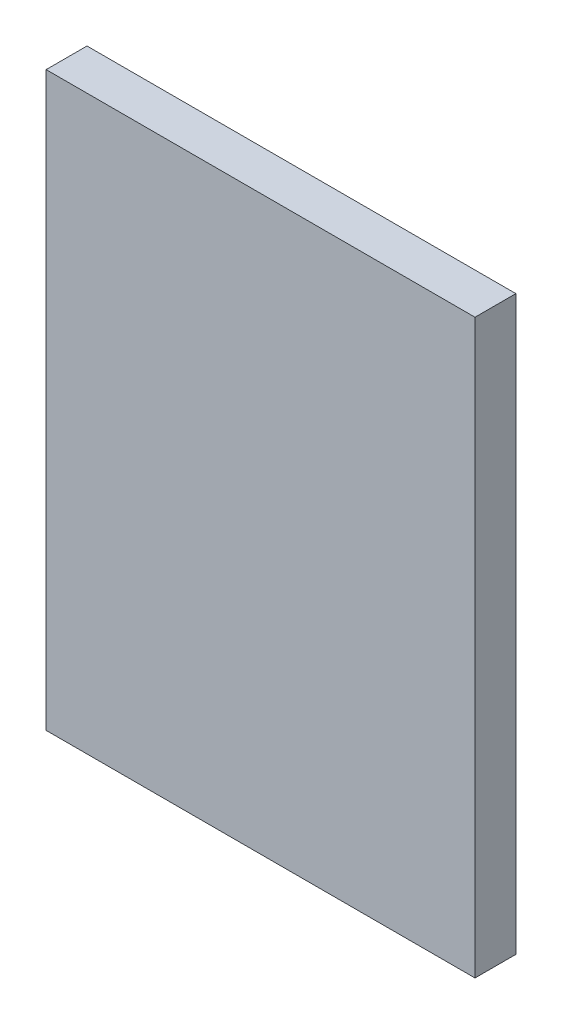
SolidWorks part; units mm, degrees
ref_plane "Front Plane" through (0, 0, 0) normal (0, 0, 1) x (1, 0, 0)
ref_plane "Top Plane" through (0, 0, 0) normal (0, 1, 0) x (1, 0, 0)
ref_plane "Right Plane" through (0, 0, 0) normal (1, 0, 0) x (0, 0, -1)
sketch "m3_pcb_standoffs" plane through (0, 0, 0) normal (0, 0, 1) x (1, 0, 0)
  line L18 (-5, -5) -> (47.46, -5) construction
  line L19 (47.46, -5) -> (47.46, 45) construction
  line L20 (47.46, 45) -> (-5, 45) construction
  line L21 (-5, 45) -> (-5, -5) construction
  circle A0 centre (12.7, 35.56) radius 4.1058
  circle A1 centre (35.56, 35.56) radius 4.1058
  circle A2 centre (35.56, 5.08) radius 4.1058
  circle A3 centre (12.7, 5.08) radius 4.1058
  circle A4 centre (12.7, 35.56) radius 1.6
  circle A5 centre (35.56, 35.56) radius 1.6
  circle A6 centre (35.56, 5.08) radius 1.6
  circle A7 centre (12.7, 5.08) radius 1.6
extrude "Boss-Extrude1" add sketch "m3_pcb_standoffs" along normal blind 5
ref_plane "BasePlane" through (0, 0, 5) normal (0, 0, 1) x (1, 0, 0)
sketch "Base" plane through (0, 0, 5) normal (0, 0, 1) x (1, 0, 0)
  line L0 (-5, 45) -> (-5, -5) construction
  line L1 (-5, 55) -> (47.46, 55)
  line L2 (-5, 55) -> (-5, -15)
  line L3 (-5, -15) -> (47.46, -15)
  line L4 (47.46, 55) -> (47.46, -15)
  line L5 (-5, -5) -> (47.46, -5) construction
  line L6 (47.46, -5) -> (47.46, 45) construction
  line L7 (47.46, 45) -> (-5, 45) construction
  dimension "D1" = 0
  dimension "D2" = 10
  dimension "D3" = 0
  dimension "D4" = 10
extrude "Boss-Extrude2" add sketch "Base" along normal blind 5
